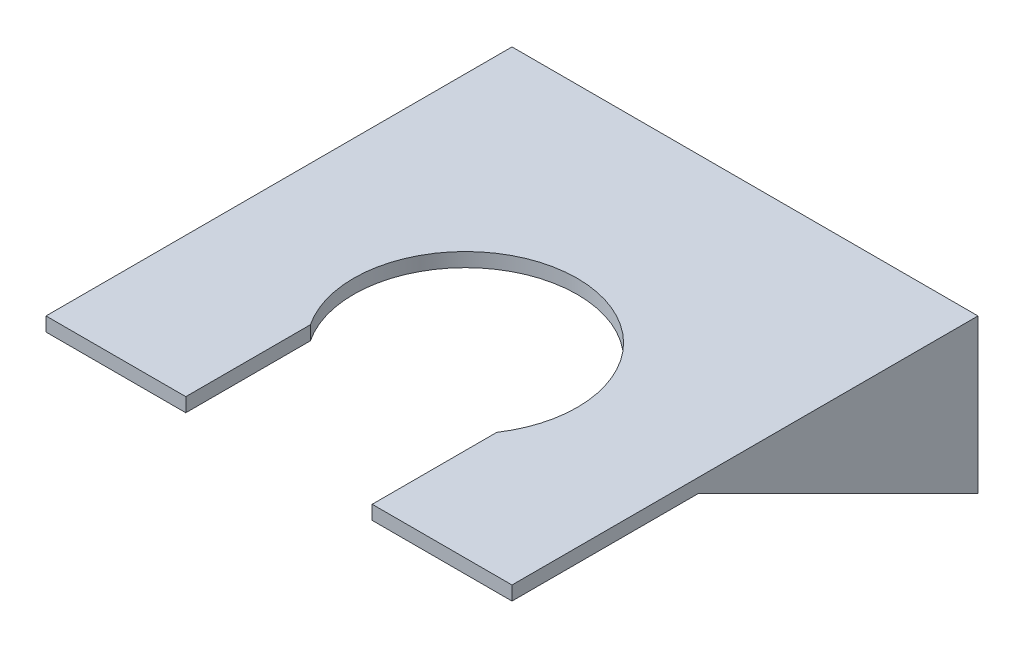
SolidWorks part; units mm, degrees
ref_plane "Front Plane" through (0, 0, 0) normal (0, 0, 1) x (1, 0, 0)
ref_plane "Top Plane" through (0, 0, 0) normal (0, 1, 0) x (1, 0, 0)
ref_plane "Right Plane" through (0, 0, 0) normal (1, 0, 0) x (0, 0, -1)
sketch "Sketch1" plane through (0, 0, 0) normal (0, 0, 1) x (1, 0, 0)
  line L1 (-25, -1.0618) -> (25, -1.0618)
  line L2 (-25, -1.0618) -> (-25, -2.5618)
  line L3 (-25, -2.5618) -> (25, -2.5618)
  line L4 (25, -1.0618) -> (25, -2.5618)
  point P6 (0, -1.0618)
  dimension "D1" = 1.5
  dimension "D3" = 50
extrude "Boss-Extrude1" add sketch "Sketch1" along normal blind 50
sketch "Sketch2" plane through (0, -1.0618, 0) normal (0, 1, 0) x (1, 0, 0)
  line L0 (-25, -30) -> (25, -30) construction
  line L1 (-25, -50) -> (-25, 0) construction
  line L2 (25, -50) -> (25, 0) construction
  line L3 (-10, -36.6332) -> (-10, -50)
  line L5 (10, -36.6332) -> (10, -50)
  line L6 (25, 0) -> (-25, 0) construction
  line L7 (-10, -50) -> (10, -50)
  arc A0 (10, -36.6332) -> (-10, -36.6332) centre (0, -30) ccw
  dimension "D2" = 24
  dimension "D1" = 30
  dimension "D3" = 10
  dimension "D4" = 10
extrude "Cut-Extrude1" cut sketch "Sketch2" against normal up to surface (1.5 mm away) up to face at (0, -2.5618, 25)
ref_plane "Plane4" through (-20, 0, 0) normal (-1, 0, 0) x (0, 0, 1)
sketch "Sketch4" plane through (-25, 0, 0) normal (-1, 0, 0) x (0, 0, 1)
  line L0 (0, -2.5618) -> (0, -17.5618)
  line L1 (0, -17.5618) -> (30, -2.5618)
  line L2 (50, -2.5618) -> (0, -2.5618) construction
  line L3 (30, -2.5618) -> (0, -2.5618)
  dimension "D1" = 15
  dimension "D2" = 30
extrude "Boss-Extrude2" add sketch "Sketch4" against normal blind 1.5
mirror "Mirror1" about plane through (0, 0, 0) normal (1, 0, 0) of "Boss-Extrude2"
